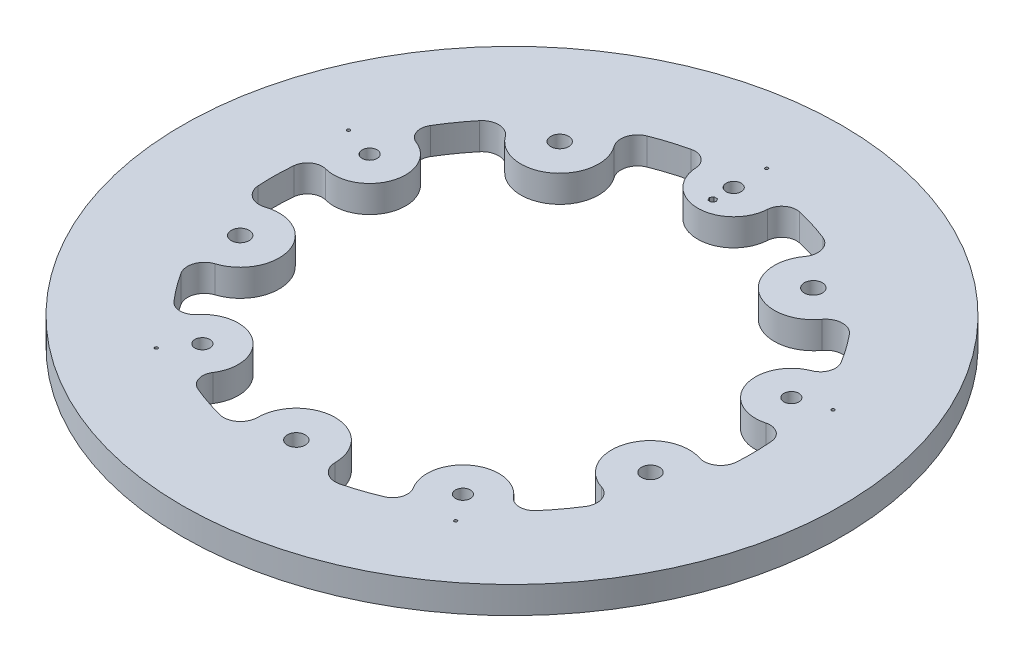
SolidWorks part; units mm, degrees
ref_plane "Front" through (0, 0, 0) normal (0, 0, 1) x (1, 0, 0)
ref_plane "Top" through (0, 0, 0) normal (0, 1, 0) x (1, 0, 0)
ref_plane "Right" through (0, 0, 0) normal (1, 0, 0) x (0, 0, -1)
sketch "Sketch2" plane through (0, 0, 0) normal (0, 1, 0) x (1, 0, 0)
  line L0 (0, 0) -> (0, 110) construction
  line L1 (0, 0) -> (104.6162, 33.9919) construction
  line L2 (0, 0) -> (64.6564, -88.9919) construction
  line L3 (0, 0) -> (-64.6564, -88.9919) construction
  line L4 (0, 0) -> (-104.6162, 33.9919) construction
  line L5 (0, 0) -> (0, -80) construction
  line L6 (-10.8095, -80) -> (10.8095, -80) construction
  line L7 (-12.6491, -75) -> (12.6491, -75) construction
  line L8 (-13, -72) -> (13, -72) construction
  line L9 (-13, -72) -> (-13, -52.7888) construction
  line L10 (0, 0) -> (-76.0845, -24.7214) construction
  line L11 (-75.238, -11.1463) -> (-67.4204, -35.2063) construction
  line L12 (-72.4933, -9.8855) -> (-64.4588, -34.613) construction
  line L14 (0, 0) -> (-47.0228, 64.7214) construction
  line L15 (-33.8505, 68.1112) -> (-54.3172, 53.2413) construction
  line L16 (-31.8033, 65.8904) -> (-52.8378, 50.608) construction
  line L17 (-47.0228, 64.7214) -> (-55.7679, 58.3677) construction
  line L18 (0, 0) -> (47.0228, 64.7214) construction
  line L19 (54.3172, 53.2413) -> (33.8505, 68.1112) construction
  line L20 (52.8378, 50.608) -> (31.8033, 65.8904) construction
  line L21 (55.7679, 58.3677) -> (38.2778, 71.075) construction
  line L22 (0, 0) -> (76.0845, -24.7214) construction
  line L23 (67.4204, -35.2063) -> (75.238, -11.1463) construction
  line L24 (64.4588, -34.613) -> (72.4933, -9.8855) construction
  line L25 (72.7442, -35.0018) -> (79.4248, -14.4409) construction
  line L26 (-79.4248, -14.4409) -> (-76.0845, -24.7214) construction
  arc A0 (-18.1052, 77.9243) -> (-29.3118, 74.4367) centre (0, 0) ccw
  circle A1 centre (0, 0) radius 110
  circle A2 centre (0, 74) radius 6 construction
  circle A3 centre (0, 74) radius 2
  arc A4 (-11.9814, 73.3323) -> (11.9814, 73.3323) centre (0, 74) ccw
  circle A5 centre (70.3782, 22.8673) radius 2
  circle A6 centre (70.3782, 22.8673) radius 6 construction
  arc A7 (66.0407, 34.0559) -> (73.4456, 11.2659) centre (70.3782, 22.8673) ccw
  circle A8 centre (43.4961, -59.8673) radius 2
  circle A9 centre (43.4961, -59.8673) radius 6 construction
  arc A10 (52.7968, -52.2846) -> (33.4105, -66.3696) centre (43.4961, -59.8673) ccw
  circle A11 centre (-43.4961, -59.8673) radius 2
  circle A12 centre (-43.4961, -59.8673) radius 6 construction
  arc A13 (-33.4105, -66.3696) -> (-52.7968, -52.2846) centre (-43.4961, -59.8673) ccw
  circle A14 centre (-70.3782, 22.8673) radius 2
  circle A15 centre (-70.3782, 22.8673) radius 6 construction
  arc A16 (-73.4456, 11.2659) -> (-66.0407, 34.0559) centre (-70.3782, 22.8673) ccw
  arc A17 (68.5156, 41.299) -> (61.7356, 50.8794) centre (0, 0) ccw
  arc A18 (60.4502, -52.4001) -> (67.4665, -42.9915) centre (0, 0) ccw
  arc A19 (-31.1553, -73.6841) -> (-20.039, -77.4496) centre (0, 0) ccw
  arc A20 (-79.7053, 6.8608) -> (-79.8513, -4.875) centre (0, 0) ccw
  circle A21 centre (0, -72) radius 3
  arc A22 (-13, -72) -> (13, -72) centre (0, -72) cw
  arc A23 (-13, -72) -> (-20.039, -77.4496) centre (-18.629, -72) cw
  arc A24 (13, -72) -> (20.039, -77.4496) centre (18.629, -72) ccw
  arc A25 (-72.4933, -9.8855) -> (-79.8513, -4.875) centre (-74.2328, -4.532) cw
  circle A26 centre (-68.4761, -22.2492) radius 3
  arc A27 (-72.4933, -9.8855) -> (-64.4588, -34.613) centre (-68.4761, -22.2492) cw
  arc A28 (-64.4588, -34.613) -> (-67.4665, -42.9915) centre (-62.7194, -39.9665) ccw
  arc A29 (-31.8033, 65.8904) -> (-29.3118, 74.4367) centre (-27.2493, 69.1991) cw
  circle A30 centre (-42.3205, 58.2492) radius 3
  arc A31 (-31.8033, 65.8904) -> (-52.8378, 50.608) centre (-42.3205, 58.2492) cw
  arc A32 (-52.8378, 50.608) -> (-61.7356, 50.8794) centre (-57.3917, 47.2994) ccw
  arc A33 (52.8378, 50.608) -> (61.7356, 50.8794) centre (57.3917, 47.2994) cw
  circle A34 centre (42.3205, 58.2492) radius 3
  arc A35 (52.8378, 50.608) -> (31.8033, 65.8904) centre (42.3205, 58.2492) cw
  arc A36 (31.8033, 65.8904) -> (29.3118, 74.4367) centre (27.2493, 69.1991) ccw
  arc A37 (64.4588, -34.613) -> (67.4665, -42.9915) centre (62.7194, -39.9665) cw
  circle A38 centre (68.4761, -22.2492) radius 3
  arc A39 (64.4588, -34.613) -> (72.4933, -9.8855) centre (68.4761, -22.2492) cw
  arc A40 (72.4933, -9.8855) -> (79.8513, -4.875) centre (74.2328, -4.532) ccw
  arc A41 (20.039, -77.4496) -> (31.1553, -73.6841) centre (0, 0) ccw
  arc A42 (-20.039, -77.4496) -> (20.039, -77.4496) centre (0, 0) ccw construction
  arc A43 (79.8513, -4.875) -> (79.7053, 6.8608) centre (0, 0) ccw
  arc A44 (29.3118, 74.4367) -> (18.1052, 77.9243) centre (0, 0) ccw
  arc A45 (-61.7356, 50.8794) -> (-68.5156, 41.299) centre (0, 0) ccw
  arc A46 (-67.4665, -42.9915) -> (-60.4502, -52.4001) centre (0, 0) ccw
  arc A47 (-66.0407, 34.0559) -> (-68.5156, 41.299) centre (-64.2334, 38.7179) cw
  arc A48 (-73.4456, 11.2659) -> (-79.7053, 6.8608) centre (-74.7237, 6.432) ccw
  arc A49 (-52.7968, -52.2846) -> (-60.4502, -52.4001) centre (-56.6721, -49.1251) cw
  arc A50 (-33.4105, -66.3696) -> (-31.1553, -73.6841) centre (-29.2081, -69.0788) ccw
  arc A51 (52.7968, -52.2846) -> (60.4502, -52.4001) centre (56.6721, -49.1251) ccw
  arc A52 (33.4105, -66.3696) -> (31.1553, -73.6841) centre (29.2081, -69.0788) cw
  arc A53 (73.4456, 11.2659) -> (79.7053, 6.8608) centre (74.7237, 6.432) cw
  arc A54 (66.0407, 34.0559) -> (68.5156, 41.299) centre (64.2334, 38.7179) ccw
  arc A55 (-11.9814, 73.3323) -> (-18.1052, 77.9243) centre (-16.9737, 73.0541) ccw
  arc A56 (11.9814, 73.3323) -> (18.1052, 77.9243) centre (16.9737, 73.0541) cw
  point P36 (0, 0)
  point P38 (0, -80)
  point P39 (0, -80)
  point P44 (0, -75)
  point P51 (0, -72)
  point P111 (0, 0)
  dimension "D1" = 160
  dimension "D2" = 30
  dimension "D3" = 12
  dimension "D4" = 4
  dimension "D5" = 6
  dimension "D6" = 5
  dimension "D7" = 6
  dimension "D9" = 10
  dimension "D11" = 5
  dimension "D8" = 5
  dimension "D10" = 5
extrude "Boss-Extrude1" add sketch "Sketch2" along normal blind 9
sketch "Sketch3" [suppressed] plane through (0, 9, 0) normal (0, 1, 0) x (1, 0, 0)
  line L0 (0, 0) -> (0, 116.2564) construction
  line L1 (4.9616, 114.4288) -> (5.0361, 116.1472) construction
  line L2 (0, 114.5364) -> (0, 115.3964) construction
  line L3 (4.9616, 114.4288) -> (4.9988, 115.288) construction
  circle A0 centre (0, 0) radius 116.2564 construction
  circle A1 centre (0, 0) radius 112.4564 construction
  circle A2 centre (0, 0) radius 114.5364 construction
  arc A3 (-2.0799, 114.5175) -> (2.0799, 114.5175) centre (0, 114.5364) ccw
  arc A4 (2.8828, 114.5001) -> (7.0387, 114.3199) centre (4.9616, 114.4288) ccw
  arc A5 (7.8401, 114.2677) -> (11.9843, 113.9077) centre (9.9138, 114.1065) ccw
  arc A6 (12.7827, 113.8208) -> (16.9074, 113.2816) centre (14.8475, 113.5699) ccw
  arc A7 (17.7012, 113.1603) -> (21.7987, 112.4428) centre (19.7532, 112.8202) ccw
  arc A8 (22.5866, 112.2872) -> (26.6492, 111.393) centre (24.6219, 111.8586) ccw
  arc A9 (27.4295, 111.2034) -> (31.4495, 110.134) centre (29.4444, 110.687) ccw
  arc A10 (32.221, 109.9108) -> (36.1909, 108.6683) centre (34.2116, 109.3076) ccw
  arc A11 (36.9519, 108.4119) -> (40.8643, 106.9985) centre (38.9145, 107.723) ccw
  arc A12 (41.6135, 106.7094) -> (45.461, 105.1279) centre (43.5444, 105.9361) ccw
  arc A13 (46.197, 104.8066) -> (49.9723, 103.0599) centre (48.0926, 103.9504) ccw
  arc A14 (50.6937, 102.707) -> (54.3898, 100.7984) centre (52.5504, 101.7695) ccw
  arc A15 (55.0952, 100.4146) -> (58.7052, 98.3477) centre (56.9096, 99.3975) ccw
  arc A16 (59.3934, 97.9337) -> (62.9104, 95.7124) centre (61.162, 96.839) ccw
  arc A17 (63.58, 95.2689) -> (66.9975, 92.8973) centre (65.2995, 94.0986) ccw
  arc A18 (67.6472, 92.4253) -> (70.9588, 89.9079) centre (69.3145, 91.1816) ccw
  arc A19 (71.5875, 89.4081) -> (74.7869, 86.7496) centre (73.1993, 88.0934) ccw
  arc A20 (75.3933, 86.2231) -> (78.4746, 83.4285) centre (76.9466, 84.8398) ccw
  arc A21 (79.0576, 82.8762) -> (82.015, 79.9508) centre (80.5496, 81.4269) ccw
  arc A22 (82.5735, 79.3738) -> (85.4013, 76.3229) centre (84.0013, 77.8612) ccw
  arc A23 (85.9344, 75.7223) -> (88.6274, 72.5518) centre (87.2953, 74.1493) ccw
  arc A24 (89.1339, 71.9286) -> (91.687, 68.6445) centre (90.4254, 70.2981) ccw
  arc A25 (92.1661, 67.9999) -> (94.5746, 64.6083) centre (93.3857, 66.315) ccw
  arc A26 (95.0252, 63.9436) -> (97.2845, 60.4508) centre (96.1707, 62.2074) ccw
  arc A27 (97.706, 59.7672) -> (99.8119, 56.1798) centre (98.7752, 57.983) ccw
  arc A28 (100.2033, 55.4786) -> (102.1518, 51.8033) centre (101.1943, 53.6498) ccw
  arc A29 (102.5125, 51.0858) -> (104.3, 47.3296) centre (103.4233, 49.2158) ccw
  arc A30 (104.6293, 46.5972) -> (106.2523, 42.767) centre (105.4582, 44.6895) ccw
  arc A31 (106.5496, 42.021) -> (108.0052, 38.1242) centre (107.2951, 40.0792) ccw
  arc A32 (108.2699, 37.366) -> (109.5553, 33.4097) centre (108.9306, 35.3937) ccw
  arc A33 (109.7869, 32.6408) -> (110.8997, 28.6326) centre (110.3615, 30.6417) ccw
  arc A34 (111.0978, 27.8543) -> (112.036, 23.8017) centre (111.5853, 25.8322) ccw
  arc A35 (112.2001, 23.0155) -> (112.9619, 18.9261) centre (112.5996, 20.9743) ccw
  arc A36 (113.0918, 18.1336) -> (113.6757, 14.0149) centre (113.4024, 16.0769) ccw
  arc A37 (113.7712, 13.2175) -> (114.1761, 9.0775) centre (113.9924, 11.1493) ccw
  arc A38 (114.2369, 8.2767) -> (114.4621, 4.123) centre (114.3684, 6.2009) ccw
  arc A39 (114.4882, 3.3203) -> (114.5333, -0.8392) centre (114.5296, 1.2408) ccw
  arc A40 (114.5246, -1.6423) -> (114.3894, -5.7999) centre (114.4759, -3.7217) ccw
  arc A41 (114.3459, -6.6018) -> (114.0308, -10.7497) centre (114.2072, -8.6771) ccw
  arc A42 (113.9526, -11.5489) -> (113.4581, -15.6792) centre (113.7241, -13.6163) ccw
  arc A43 (113.3454, -16.4744) -> (112.6724, -20.5794) centre (113.0275, -18.5299) ccw
  arc A44 (112.5253, -21.3689) -> (111.6752, -25.4409) centre (112.1187, -23.4087) ccw
  arc A45 (111.494, -26.2233) -> (110.4683, -30.2546) centre (110.9994, -28.2436) ccw
  arc A46 (110.2534, -31.0284) -> (109.054, -35.0116) centre (109.6718, -33.0255) ccw
  arc A47 (108.8058, -35.7753) -> (107.4349, -39.7028) centre (108.1382, -37.7453) ccw
  arc A48 (107.1539, -40.4551) -> (105.6142, -44.3195) centre (106.4016, -42.3943) ccw
  arc A49 (105.3009, -45.0589) -> (103.5952, -48.853) centre (104.4653, -46.9637) ccw
  arc A50 (103.2501, -49.5781) -> (101.3817, -53.2947) centre (102.3328, -51.4449) ccw
  arc A51 (101.0056, -54.0042) -> (98.9779, -57.6364) centre (100.0082, -55.8295) ccw
  arc A52 (98.5713, -58.329) -> (96.3882, -61.8699) centre (97.4959, -60.1093) ccw
  arc A53 (95.9521, -62.5442) -> (93.6176, -65.9872) centre (94.8005, -64.2763) ccw
  arc A54 (93.1527, -66.642) -> (90.6713, -69.9807) centre (91.9271, -68.3226) ccw
  arc A55 (90.1784, -70.6147) -> (87.5547, -73.8428) centre (88.8812, -72.2407) ccw
  arc A56 (87.0348, -74.4548) -> (84.2737, -77.5662) centre (85.6684, -76.0231) ccw
  arc A57 (83.7278, -78.1552) -> (80.8345, -81.144) centre (82.2947, -79.6628) ccw
  arc A58 (80.2636, -81.7088) -> (77.2436, -84.5695) centre (78.7666, -83.1529) ccw
  arc A59 (76.6487, -85.109) -> (73.5076, -87.8362) centre (75.0906, -86.4869) ccw
  arc A60 (72.89, -88.3495) -> (69.6337, -90.938) centre (71.2736, -89.6585) ccw
  arc A61 (68.9944, -91.424) -> (65.629, -93.8691) centre (67.3228, -92.6619) ccw
  arc A62 (64.9692, -94.327) -> (61.5011, -96.624) centre (63.2456, -95.4912) ccw
  arc A63 (60.8221, -97.0528) -> (57.2577, -99.1974) centre (59.0497, -98.1413) ccw
  arc A64 (56.5608, -99.5964) -> (52.9069, -101.5846) centre (54.7429, -100.6071) ccw
  arc A65 (52.1933, -101.9531) -> (48.4567, -103.7811) centre (50.3333, -102.8841) ccw
  arc A66 (47.7279, -104.1183) -> (43.9155, -105.7828) centre (45.8293, -104.9679) ccw
  arc A67 (43.1728, -106.0881) -> (39.2919, -107.5859) centre (41.2392, -106.8546) ccw
  arc A68 (38.5366, -107.8587) -> (34.5946, -109.187) centre (36.5716, -108.5407) ccw
  arc A69 (33.8282, -109.4268) -> (29.8323, -110.5831) centre (31.8355, -110.0231) ccw
  arc A70 (29.0562, -110.7895) -> (25.0139, -111.7716) centre (27.0395, -111.2989) ccw
  arc A71 (24.2296, -111.9442) -> (20.1486, -112.7502) centre (22.1928, -112.3657) ccw
  arc A72 (19.3576, -112.8887) -> (15.2455, -113.5172) centre (17.3044, -113.2216) ccw
  arc A73 (14.4492, -113.6213) -> (10.3138, -114.071) centre (12.3836, -113.8649) ccw
  arc A74 (9.5137, -114.1406) -> (5.3627, -114.4107) centre (7.4394, -114.2945) ccw
  arc A75 (4.5604, -114.4455) -> (0.4015, -114.5357) centre (2.4814, -114.5095) ccw
  arc A76 (-0.4015, -114.5357) -> (-4.5604, -114.4455) centre (-2.4814, -114.5095) ccw
  arc A77 (-5.3627, -114.4107) -> (-9.5137, -114.1406) centre (-7.4394, -114.2945) ccw
  arc A78 (-10.3138, -114.071) -> (-14.4492, -113.6213) centre (-12.3836, -113.8649) ccw
  arc A79 (-15.2455, -113.5172) -> (-19.3576, -112.8887) centre (-17.3044, -113.2216) ccw
  arc A80 (-20.1486, -112.7502) -> (-24.2296, -111.9442) centre (-22.1928, -112.3657) ccw
  arc A81 (-25.0139, -111.7716) -> (-29.0562, -110.7895) centre (-27.0395, -111.2989) ccw
  arc A82 (-29.8323, -110.5831) -> (-33.8282, -109.4268) centre (-31.8355, -110.0231) ccw
  arc A83 (-34.5946, -109.187) -> (-38.5366, -107.8587) centre (-36.5716, -108.5407) ccw
  arc A84 (-39.2919, -107.5859) -> (-43.1728, -106.0881) centre (-41.2392, -106.8546) ccw
  arc A85 (-43.9155, -105.7828) -> (-47.7279, -104.1183) centre (-45.8293, -104.9679) ccw
  arc A86 (-48.4567, -103.7811) -> (-52.1933, -101.9531) centre (-50.3333, -102.8841) ccw
  arc A87 (-52.9069, -101.5846) -> (-56.5608, -99.5964) centre (-54.7429, -100.6071) ccw
  arc A88 (-57.2577, -99.1974) -> (-60.8221, -97.0528) centre (-59.0497, -98.1413) ccw
  arc A89 (-61.5011, -96.624) -> (-64.9692, -94.327) centre (-63.2456, -95.4912) ccw
  arc A90 (-65.629, -93.8691) -> (-68.9944, -91.424) centre (-67.3228, -92.6619) ccw
  arc A91 (-69.6337, -90.938) -> (-72.89, -88.3495) centre (-71.2736, -89.6585) ccw
  arc A92 (-73.5076, -87.8362) -> (-76.6487, -85.109) centre (-75.0906, -86.4869) ccw
  arc A93 (-77.2436, -84.5695) -> (-80.2636, -81.7088) centre (-78.7666, -83.1529) ccw
  arc A94 (-80.8345, -81.144) -> (-83.7278, -78.1552) centre (-82.2947, -79.6628) ccw
  arc A95 (-84.2737, -77.5662) -> (-87.0348, -74.4548) centre (-85.6684, -76.0231) ccw
  arc A96 (-87.5547, -73.8428) -> (-90.1784, -70.6147) centre (-88.8812, -72.2407) ccw
  arc A97 (-90.6713, -69.9807) -> (-93.1527, -66.642) centre (-91.9271, -68.3226) ccw
  arc A98 (-93.6176, -65.9872) -> (-95.9521, -62.5442) centre (-94.8005, -64.2763) ccw
  arc A99 (-96.3882, -61.8699) -> (-98.5713, -58.329) centre (-97.4959, -60.1093) ccw
  arc A100 (-98.9779, -57.6364) -> (-101.0056, -54.0042) centre (-100.0082, -55.8295) ccw
  arc A101 (-101.3817, -53.2947) -> (-103.2501, -49.5781) centre (-102.3328, -51.4449) ccw
  arc A102 (-103.5952, -48.853) -> (-105.3009, -45.0589) centre (-104.4653, -46.9637) ccw
  arc A103 (-105.6142, -44.3195) -> (-107.1539, -40.4551) centre (-106.4016, -42.3943) ccw
  arc A104 (-107.4349, -39.7028) -> (-108.8058, -35.7753) centre (-108.1382, -37.7453) ccw
  arc A105 (-109.054, -35.0116) -> (-110.2534, -31.0284) centre (-109.6718, -33.0255) ccw
  arc A106 (-110.4683, -30.2546) -> (-111.494, -26.2233) centre (-110.9994, -28.2436) ccw
  arc A107 (-111.6752, -25.4409) -> (-112.5253, -21.3689) centre (-112.1187, -23.4087) ccw
  arc A108 (-112.6724, -20.5794) -> (-113.3454, -16.4744) centre (-113.0275, -18.5299) ccw
  arc A109 (-113.4581, -15.6792) -> (-113.9526, -11.5489) centre (-113.7241, -13.6163) ccw
  arc A110 (-114.0308, -10.7497) -> (-114.3459, -6.6018) centre (-114.2072, -8.6771) ccw
  arc A111 (-114.3894, -5.7999) -> (-114.5246, -1.6423) centre (-114.4759, -3.7217) ccw
  arc A112 (-114.5333, -0.8392) -> (-114.4882, 3.3203) centre (-114.5296, 1.2408) ccw
  arc A113 (-114.4621, 4.123) -> (-114.2369, 8.2767) centre (-114.3684, 6.2009) ccw
  arc A114 (-114.1761, 9.0775) -> (-113.7712, 13.2175) centre (-113.9924, 11.1493) ccw
  arc A115 (-113.6757, 14.0149) -> (-113.0918, 18.1336) centre (-113.4024, 16.0769) ccw
  arc A116 (-112.9619, 18.9261) -> (-112.2001, 23.0155) centre (-112.5996, 20.9743) ccw
  arc A117 (-112.036, 23.8017) -> (-111.0978, 27.8543) centre (-111.5853, 25.8322) ccw
  arc A118 (-110.8997, 28.6326) -> (-109.7869, 32.6408) centre (-110.3615, 30.6417) ccw
  arc A119 (-109.5553, 33.4097) -> (-108.2699, 37.366) centre (-108.9306, 35.3937) ccw
  arc A120 (-108.0052, 38.1242) -> (-106.5496, 42.021) centre (-107.2951, 40.0792) ccw
  arc A121 (-106.2523, 42.767) -> (-104.6293, 46.5972) centre (-105.4582, 44.6895) ccw
  arc A122 (-104.3, 47.3296) -> (-102.5125, 51.0858) centre (-103.4233, 49.2158) ccw
  arc A123 (-102.1518, 51.8033) -> (-100.2033, 55.4786) centre (-101.1943, 53.6498) ccw
  arc A124 (-99.8119, 56.1798) -> (-97.706, 59.7672) centre (-98.7752, 57.983) ccw
  arc A125 (-97.2845, 60.4508) -> (-95.0252, 63.9436) centre (-96.1707, 62.2074) ccw
  arc A126 (-94.5746, 64.6083) -> (-92.1661, 67.9999) centre (-93.3857, 66.315) ccw
  arc A127 (-91.687, 68.6445) -> (-89.1339, 71.9286) centre (-90.4254, 70.2981) ccw
  arc A128 (-88.6274, 72.5518) -> (-85.9344, 75.7223) centre (-87.2953, 74.1493) ccw
  arc A129 (-85.4013, 76.3229) -> (-82.5735, 79.3738) centre (-84.0013, 77.8612) ccw
  arc A130 (-82.015, 79.9508) -> (-79.0576, 82.8762) centre (-80.5496, 81.4269) ccw
  arc A131 (-78.4746, 83.4285) -> (-75.3933, 86.2231) centre (-76.9466, 84.8398) ccw
  arc A132 (-74.7869, 86.7496) -> (-71.5875, 89.4081) centre (-73.1993, 88.0934) ccw
  arc A133 (-70.9588, 89.9079) -> (-67.6472, 92.4253) centre (-69.3145, 91.1816) ccw
  arc A134 (-66.9975, 92.8973) -> (-63.58, 95.2689) centre (-65.2995, 94.0986) ccw
  arc A135 (-62.9104, 95.7124) -> (-59.3934, 97.9337) centre (-61.162, 96.839) ccw
  arc A136 (-58.7052, 98.3477) -> (-55.0952, 100.4146) centre (-56.9096, 99.3975) ccw
  arc A137 (-54.3898, 100.7984) -> (-50.6937, 102.707) centre (-52.5504, 101.7695) ccw
  arc A138 (-49.9723, 103.0599) -> (-46.197, 104.8066) centre (-48.0926, 103.9504) ccw
  arc A139 (-45.461, 105.1279) -> (-41.6135, 106.7094) centre (-43.5444, 105.9361) ccw
  arc A140 (-40.8643, 106.9985) -> (-36.9519, 108.4119) centre (-38.9145, 107.723) ccw
  arc A141 (-36.1909, 108.6683) -> (-32.221, 109.9108) centre (-34.2116, 109.3076) ccw
  arc A142 (-31.4495, 110.134) -> (-27.4295, 111.2034) centre (-29.4444, 110.687) ccw
  arc A143 (-26.6492, 111.393) -> (-22.5866, 112.2872) centre (-24.6219, 111.8586) ccw
  arc A144 (-21.7987, 112.4428) -> (-17.7012, 113.1603) centre (-19.7532, 112.8202) ccw
  arc A145 (-16.9074, 113.2816) -> (-12.7827, 113.8208) centre (-14.8475, 113.5699) ccw
  arc A146 (-11.9843, 113.9077) -> (-7.8401, 114.2677) centre (-9.9138, 114.1065) ccw
  arc A147 (-7.0387, 114.3199) -> (-2.8828, 114.5001) centre (-4.9616, 114.4288) ccw
  arc A148 (2.0799, 114.5175) -> (2.8828, 114.5001) centre (0, 0) cw
  arc A149 (7.0387, 114.3199) -> (7.8401, 114.2677) centre (0, 0) cw
  arc A150 (11.9843, 113.9077) -> (12.7827, 113.8208) centre (0, 0) cw
  arc A151 (16.9074, 113.2816) -> (17.7012, 113.1603) centre (0, 0) cw
  arc A152 (21.7987, 112.4428) -> (22.5866, 112.2872) centre (0, 0) cw
  arc A153 (26.6492, 111.393) -> (27.4295, 111.2034) centre (0, 0) cw
  arc A154 (31.4495, 110.134) -> (32.221, 109.9108) centre (0, 0) cw
  arc A155 (36.1909, 108.6683) -> (36.9519, 108.4119) centre (0, 0) cw
  arc A156 (40.8643, 106.9985) -> (41.6135, 106.7094) centre (0, 0) cw
  arc A157 (45.461, 105.1279) -> (46.197, 104.8066) centre (0, 0) cw
  arc A158 (49.9723, 103.0599) -> (50.6937, 102.707) centre (0, 0) cw
  arc A159 (54.3898, 100.7984) -> (55.0952, 100.4146) centre (0, 0) cw
  arc A160 (58.7052, 98.3477) -> (59.3934, 97.9337) centre (0, 0) cw
  arc A161 (62.9104, 95.7124) -> (63.58, 95.2689) centre (0, 0) cw
  arc A162 (66.9975, 92.8973) -> (67.6472, 92.4253) centre (0, 0) cw
  arc A163 (70.9588, 89.9079) -> (71.5875, 89.4081) centre (0, 0) cw
  arc A164 (74.7869, 86.7496) -> (75.3933, 86.2231) centre (0, 0) cw
  arc A165 (78.4746, 83.4285) -> (79.0576, 82.8762) centre (0, 0) cw
  arc A166 (82.015, 79.9508) -> (82.5735, 79.3738) centre (0, 0) cw
  arc A167 (85.4013, 76.3229) -> (85.9344, 75.7223) centre (0, 0) cw
  arc A168 (88.6274, 72.5518) -> (89.1339, 71.9286) centre (0, 0) cw
  arc A169 (91.687, 68.6445) -> (92.1661, 67.9999) centre (0, 0) cw
  arc A170 (94.5746, 64.6083) -> (95.0252, 63.9436) centre (0, 0) cw
  arc A171 (97.2845, 60.4508) -> (97.706, 59.7672) centre (0, 0) cw
  arc A172 (99.8119, 56.1798) -> (100.2033, 55.4786) centre (0, 0) cw
  arc A173 (102.1518, 51.8033) -> (102.5125, 51.0858) centre (0, 0) cw
  arc A174 (104.3, 47.3296) -> (104.6293, 46.5972) centre (0, 0) cw
  arc A175 (106.2523, 42.767) -> (106.5496, 42.021) centre (0, 0) cw
  arc A176 (108.0052, 38.1242) -> (108.2699, 37.366) centre (0, 0) cw
  arc A177 (109.5553, 33.4097) -> (109.7869, 32.6408) centre (0, 0) cw
  arc A178 (110.8997, 28.6326) -> (111.0978, 27.8543) centre (0, 0) cw
  arc A179 (112.036, 23.8017) -> (112.2001, 23.0155) centre (0, 0) cw
  arc A180 (112.9619, 18.9261) -> (113.0918, 18.1336) centre (0, 0) cw
  arc A181 (113.6757, 14.0149) -> (113.7712, 13.2175) centre (0, 0) cw
  arc A182 (114.1761, 9.0775) -> (114.2369, 8.2767) centre (0, 0) cw
  arc A183 (114.4621, 4.123) -> (114.4882, 3.3203) centre (0, 0) cw
  arc A184 (114.5333, -0.8392) -> (114.5246, -1.6423) centre (0, 0) cw
  arc A185 (114.3894, -5.7999) -> (114.3459, -6.6018) centre (0, 0) cw
  arc A186 (114.0308, -10.7497) -> (113.9526, -11.5489) centre (0, 0) cw
  arc A187 (113.4581, -15.6792) -> (113.3454, -16.4744) centre (0, 0) cw
  arc A188 (112.6724, -20.5794) -> (112.5253, -21.3689) centre (0, 0) cw
  arc A189 (111.6752, -25.4409) -> (111.494, -26.2233) centre (0, 0) cw
  arc A190 (110.4683, -30.2546) -> (110.2534, -31.0284) centre (0, 0) cw
  arc A191 (109.054, -35.0116) -> (108.8058, -35.7753) centre (0, 0) cw
  arc A192 (107.4349, -39.7028) -> (107.1539, -40.4551) centre (0, 0) cw
  arc A193 (105.6142, -44.3195) -> (105.3009, -45.0589) centre (0, 0) cw
  arc A194 (103.5952, -48.853) -> (103.2501, -49.5781) centre (0, 0) cw
  arc A195 (101.3817, -53.2947) -> (101.0056, -54.0042) centre (0, 0) cw
  arc A196 (98.9779, -57.6364) -> (98.5713, -58.329) centre (0, 0) cw
  arc A197 (96.3882, -61.8699) -> (95.9521, -62.5442) centre (0, 0) cw
  arc A198 (93.6176, -65.9872) -> (93.1527, -66.642) centre (0, 0) cw
  arc A199 (90.6713, -69.9807) -> (90.1784, -70.6147) centre (0, 0) cw
  arc A200 (87.5547, -73.8428) -> (87.0348, -74.4548) centre (0, 0) cw
  arc A201 (84.2737, -77.5662) -> (83.7278, -78.1552) centre (0, 0) cw
  arc A202 (80.8345, -81.144) -> (80.2636, -81.7088) centre (0, 0) cw
  arc A203 (77.2436, -84.5695) -> (76.6487, -85.109) centre (0, 0) cw
  arc A204 (73.5076, -87.8362) -> (72.89, -88.3495) centre (0, 0) cw
  arc A205 (69.6337, -90.938) -> (68.9944, -91.424) centre (0, 0) cw
  arc A206 (65.629, -93.8691) -> (64.9692, -94.327) centre (0, 0) cw
  arc A207 (61.5011, -96.624) -> (60.8221, -97.0528) centre (0, 0) cw
  arc A208 (57.2577, -99.1974) -> (56.5608, -99.5964) centre (0, 0) cw
  arc A209 (52.9069, -101.5846) -> (52.1933, -101.9531) centre (0, 0) cw
  arc A210 (48.4567, -103.7811) -> (47.7279, -104.1183) centre (0, 0) cw
  arc A211 (43.9155, -105.7828) -> (43.1728, -106.0881) centre (0, 0) cw
  arc A212 (39.2919, -107.5859) -> (38.5366, -107.8587) centre (0, 0) cw
  arc A213 (34.5946, -109.187) -> (33.8282, -109.4268) centre (0, 0) cw
  arc A214 (29.8323, -110.5831) -> (29.0562, -110.7895) centre (0, 0) cw
  arc A215 (25.0139, -111.7716) -> (24.2296, -111.9442) centre (0, 0) cw
  arc A216 (20.1486, -112.7502) -> (19.3576, -112.8887) centre (0, 0) cw
  arc A217 (15.2455, -113.5172) -> (14.4492, -113.6213) centre (0, 0) cw
  arc A218 (10.3138, -114.071) -> (9.5137, -114.1406) centre (0, 0) cw
  arc A219 (5.3627, -114.4107) -> (4.5604, -114.4455) centre (0, 0) cw
  arc A220 (0.4015, -114.5357) -> (-0.4015, -114.5357) centre (0, 0) cw
  arc A221 (-4.5604, -114.4455) -> (-5.3627, -114.4107) centre (0, 0) cw
  arc A222 (-9.5137, -114.1406) -> (-10.3138, -114.071) centre (0, 0) cw
  arc A223 (-14.4492, -113.6213) -> (-15.2455, -113.5172) centre (0, 0) cw
  arc A224 (-19.3576, -112.8887) -> (-20.1486, -112.7502) centre (0, 0) cw
  arc A225 (-24.2296, -111.9442) -> (-25.0139, -111.7716) centre (0, 0) cw
  arc A226 (-29.0562, -110.7895) -> (-29.8323, -110.5831) centre (0, 0) cw
  arc A227 (-33.8282, -109.4268) -> (-34.5946, -109.187) centre (0, 0) cw
  arc A228 (-38.5366, -107.8587) -> (-39.2919, -107.5859) centre (0, 0) cw
  arc A229 (-43.1728, -106.0881) -> (-43.9155, -105.7828) centre (0, 0) cw
  arc A230 (-47.7279, -104.1183) -> (-48.4567, -103.7811) centre (0, 0) cw
  arc A231 (-52.1933, -101.9531) -> (-52.9069, -101.5846) centre (0, 0) cw
  arc A232 (-56.5608, -99.5964) -> (-57.2577, -99.1974) centre (0, 0) cw
  arc A233 (-60.8221, -97.0528) -> (-61.5011, -96.624) centre (0, 0) cw
  arc A234 (-64.9692, -94.327) -> (-65.629, -93.8691) centre (0, 0) cw
  arc A235 (-68.9944, -91.424) -> (-69.6337, -90.938) centre (0, 0) cw
  arc A236 (-72.89, -88.3495) -> (-73.5076, -87.8362) centre (0, 0) cw
  arc A237 (-76.6487, -85.109) -> (-77.2436, -84.5695) centre (0, 0) cw
  arc A238 (-80.2636, -81.7088) -> (-80.8345, -81.144) centre (0, 0) cw
  arc A239 (-83.7278, -78.1552) -> (-84.2737, -77.5662) centre (0, 0) cw
  arc A240 (-87.0348, -74.4548) -> (-87.5547, -73.8428) centre (0, 0) cw
  arc A241 (-90.1784, -70.6147) -> (-90.6713, -69.9807) centre (0, 0) cw
  arc A242 (-93.1527, -66.642) -> (-93.6176, -65.9872) centre (0, 0) cw
  arc A243 (-95.9521, -62.5442) -> (-96.3882, -61.8699) centre (0, 0) cw
  arc A244 (-98.5713, -58.329) -> (-98.9779, -57.6364) centre (0, 0) cw
  arc A245 (-101.0056, -54.0042) -> (-101.3817, -53.2947) centre (0, 0) cw
  arc A246 (-103.2501, -49.5781) -> (-103.5952, -48.853) centre (0, 0) cw
  arc A247 (-105.3009, -45.0589) -> (-105.6142, -44.3195) centre (0, 0) cw
  arc A248 (-107.1539, -40.4551) -> (-107.4349, -39.7028) centre (0, 0) cw
  arc A249 (-108.8058, -35.7753) -> (-109.054, -35.0116) centre (0, 0) cw
  arc A250 (-110.2534, -31.0284) -> (-110.4683, -30.2546) centre (0, 0) cw
  arc A251 (-111.494, -26.2233) -> (-111.6752, -25.4409) centre (0, 0) cw
  arc A252 (-112.5253, -21.3689) -> (-112.6724, -20.5794) centre (0, 0) cw
  arc A253 (-113.3454, -16.4744) -> (-113.4581, -15.6792) centre (0, 0) cw
  arc A254 (-113.9526, -11.5489) -> (-114.0308, -10.7497) centre (0, 0) cw
  arc A255 (-114.3459, -6.6018) -> (-114.3894, -5.7999) centre (0, 0) cw
  arc A256 (-114.5246, -1.6423) -> (-114.5333, -0.8392) centre (0, 0) cw
  arc A257 (-114.4882, 3.3203) -> (-114.4621, 4.123) centre (0, 0) cw
  arc A258 (-114.2369, 8.2767) -> (-114.1761, 9.0775) centre (0, 0) cw
  arc A259 (-113.7712, 13.2175) -> (-113.6757, 14.0149) centre (0, 0) cw
  arc A260 (-113.0918, 18.1336) -> (-112.9619, 18.9261) centre (0, 0) cw
  arc A261 (-112.2001, 23.0155) -> (-112.036, 23.8017) centre (0, 0) cw
  arc A262 (-111.0978, 27.8543) -> (-110.8997, 28.6326) centre (0, 0) cw
  arc A263 (-109.7869, 32.6408) -> (-109.5553, 33.4097) centre (0, 0) cw
  arc A264 (-108.2699, 37.366) -> (-108.0052, 38.1242) centre (0, 0) cw
  arc A265 (-106.5496, 42.021) -> (-106.2523, 42.767) centre (0, 0) cw
  arc A266 (-104.6293, 46.5972) -> (-104.3, 47.3296) centre (0, 0) cw
  arc A267 (-102.5125, 51.0858) -> (-102.1518, 51.8033) centre (0, 0) cw
  arc A268 (-100.2033, 55.4786) -> (-99.8119, 56.1798) centre (0, 0) cw
  arc A269 (-97.706, 59.7672) -> (-97.2845, 60.4508) centre (0, 0) cw
  arc A270 (-95.0252, 63.9436) -> (-94.5746, 64.6083) centre (0, 0) cw
  arc A271 (-92.1661, 67.9999) -> (-91.687, 68.6445) centre (0, 0) cw
  arc A272 (-89.1339, 71.9286) -> (-88.6274, 72.5518) centre (0, 0) cw
  arc A273 (-85.9344, 75.7223) -> (-85.4013, 76.3229) centre (0, 0) cw
  arc A274 (-82.5735, 79.3738) -> (-82.015, 79.9508) centre (0, 0) cw
  arc A275 (-79.0576, 82.8762) -> (-78.4746, 83.4285) centre (0, 0) cw
  arc A276 (-75.3933, 86.2231) -> (-74.7869, 86.7496) centre (0, 0) cw
  arc A277 (-71.5875, 89.4081) -> (-70.9588, 89.9079) centre (0, 0) cw
  arc A278 (-67.6472, 92.4253) -> (-66.9975, 92.8973) centre (0, 0) cw
  arc A279 (-63.58, 95.2689) -> (-62.9104, 95.7124) centre (0, 0) cw
  arc A280 (-59.3934, 97.9337) -> (-58.7052, 98.3477) centre (0, 0) cw
  arc A281 (-55.0952, 100.4146) -> (-54.3898, 100.7984) centre (0, 0) cw
  arc A282 (-50.6937, 102.707) -> (-49.9723, 103.0599) centre (0, 0) cw
  arc A283 (-46.197, 104.8066) -> (-45.461, 105.1279) centre (0, 0) cw
  arc A284 (-41.6135, 106.7094) -> (-40.8643, 106.9985) centre (0, 0) cw
  arc A285 (-36.9519, 108.4119) -> (-36.1909, 108.6683) centre (0, 0) cw
  arc A286 (-32.221, 109.9108) -> (-31.4495, 110.134) centre (0, 0) cw
  arc A287 (-27.4295, 111.2034) -> (-26.6492, 111.393) centre (0, 0) cw
  arc A288 (-22.5866, 112.2872) -> (-21.7987, 112.4428) centre (0, 0) cw
  arc A289 (-17.7012, 113.1603) -> (-16.9074, 113.2816) centre (0, 0) cw
  arc A290 (-12.7827, 113.8208) -> (-11.9843, 113.9077) centre (0, 0) cw
  arc A291 (-7.8401, 114.2677) -> (-7.0387, 114.3199) centre (0, 0) cw
  arc A292 (-2.8828, 114.5001) -> (-2.0799, 114.5175) centre (0, 0) cw
  circle A293 centre (0, 0) radius 110
  circle A294 centre (0, 0) radius 110 construction
  circle A295 centre (0, 0) radius 115.3964 construction
  point P13 (2.0799, 114.5175)
  point P310 (0, 0)
  point P312 (4.9988, 115.288)
  point P734 (0, 0)
  dimension "D1" = 3.8
  dimension "D2" = 2.08
  dimension "D3" = 145
  dimension "D4" = 5
  dimension "D5" = 145
extrude "Boss-Extrude2" [suppressed] add sketch "Sketch3" against normal up to surface (9 mm away) up to face at (0, 0, 110)
sketch "Sketch4" plane through (0, 9, 0) normal (0, 1, 0) x (1, 0, 0)
  line L0 (0, 74) -> (0, 0) construction
  line L1 (70.3782, 22.8673) -> (0, 0) construction
  line L2 (43.4961, -59.8673) -> (0, 0) construction
  line L3 (-43.4961, -59.8673) -> (0, 0) construction
  line L4 (-70.3782, 22.8673) -> (0, 0) construction
  circle A0 centre (0, 74) radius 2.5
  circle A1 centre (0, 74) radius 2 construction
  circle A2 centre (70.3782, 22.8673) radius 2.5
  circle A3 centre (43.4961, -59.8673) radius 2.5
  circle A4 centre (-43.4961, -59.8673) radius 2.5
  circle A5 centre (-70.3782, 22.8673) radius 2.5
  point P18 (0, 0)
  dimension "D1" = 5
  dimension "D2" = 5
extrude "Cut-Extrude1" cut sketch "Sketch4" against normal through all
sketch "Sketch5" plane through (0, 9, 0) normal (0, 1, 0) x (1, 0, 0)
  line L0 (0, 0) -> (0, 74) construction
  line L2 (0.5774, 66) -> (1.1547, 67)
  line L3 (1.1547, 67) -> (0.5774, 68)
  line L4 (0.5774, 68) -> (-0.5774, 68)
  line L5 (-0.5774, 68) -> (-1.1547, 67)
  line L6 (-1.1547, 67) -> (-0.5774, 66)
  line L7 (-0.5774, 66) -> (0.5774, 66)
  circle A0 centre (0, 67) radius 1 construction
  dimension "D1" = 2
  dimension "D2" = 7
extrude "Cut-Extrude2" cut sketch "Sketch5" against normal through all
sketch "Sketch6" plane through (0, 9, 0) normal (0, 1, 0) x (1, 0, 0)
  line L0 (0, 85) -> (0, 0) construction
  line L1 (80.8398, 26.2664) -> (0, 0) construction
  line L2 (49.9617, -68.7664) -> (0, 0) construction
  line L3 (-49.9617, -68.7664) -> (0, 0) construction
  line L4 (-80.8398, 26.2664) -> (0, 0) construction
  circle A0 centre (0, 0) radius 85 construction
  circle A2 centre (0, 85) radius 0.5
  circle A3 centre (80.8398, 26.2664) radius 0.5
  circle A4 centre (49.9617, -68.7664) radius 0.5
  circle A5 centre (-49.9617, -68.7664) radius 0.5
  circle A6 centre (-80.8398, 26.2664) radius 0.5
  point P16 (0, 0)
  dimension "D1" = 170
  dimension "D2" = 1
  dimension "D3" = 5
extrude "Cut-Extrude3" cut sketch "Sketch6" against normal through all
